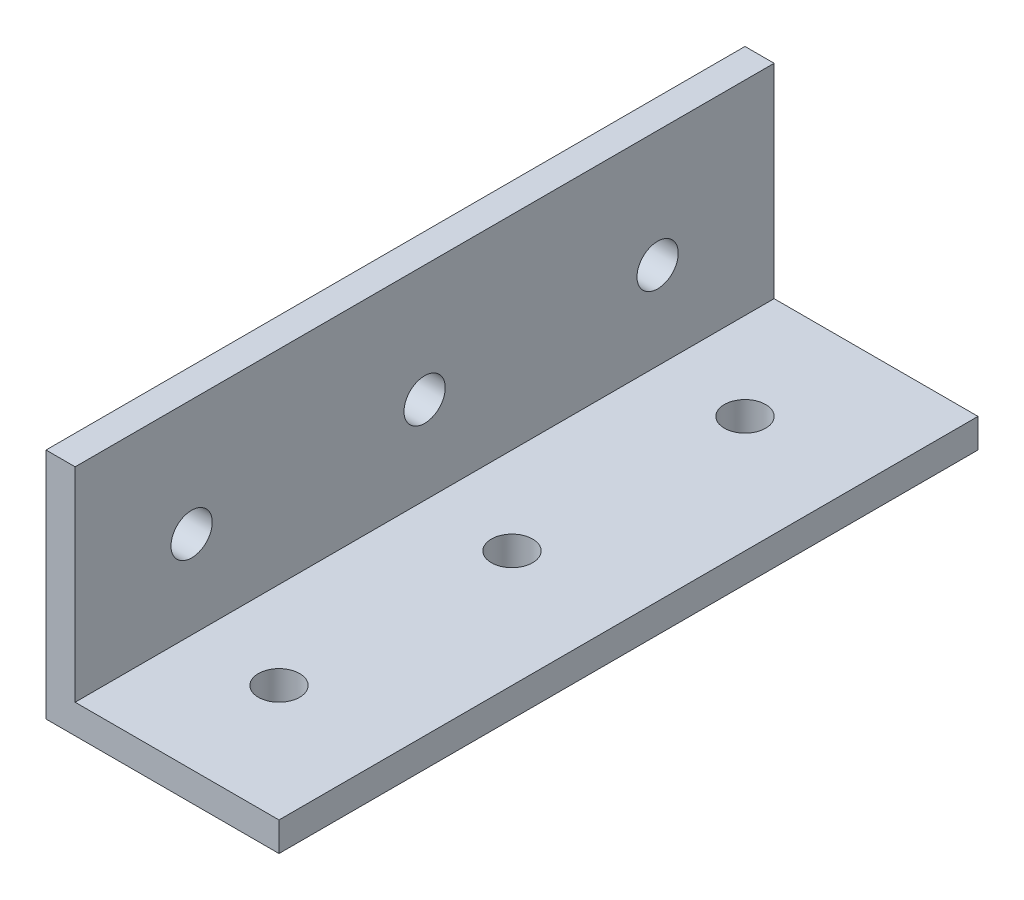
SolidWorks part; units mm, degrees
material "6061-T6 (SS)"
ref_plane "Front Plane" through (0, 0, 0) normal (0, 0, 1) x (1, 0, 0)
ref_plane "Top Plane" through (0, 0, 0) normal (0, 1, 0) x (1, 0, 0)
ref_plane "Right Plane" through (0, 0, 0) normal (1, 0, 0) x (0, 0, -1)
sketch "Sketch1" plane through (0, 0, 0) normal (0, 0, 1) x (1, 0, 0)
  line L1 (0, 0) -> (25.4, 0)
  line L2 (0, 0) -> (0, 25.4)
  line L3 (0, 25.4) -> (3.175, 25.4)
  line L4 (25.4, 0) -> (25.4, 3.175)
  line L7 (25.4, 3.175) -> (3.175, 3.175)
  line L8 (3.175, 25.4) -> (3.175, 3.175)
  dimension "D1" = 25.4
  dimension "D2" = 25.4
  dimension "D3" = 3.175
  dimension "D4" = 3.175
extrude "Boss-Extrude1" add sketch "Sketch1" along normal blind 76.2
hole_wizard "#8 Clearance Hole1" positions "Sketch3" profile "Sketch2" hole size "#8" standard "ANSI Inch" end condition through all
sketch "Sketch3" plane through (0, 0, 0) normal (0, -1, 0) x (1, 0, 0)
  line L0 (0, 76.2) -> (25.4, 76.2) construction
  line L1 (25.4, 76.2) -> (25.4, 0) construction
  point P0 (12.7, 63.5)
  point P2 (12.7, 38.1)
  point P4 (12.7, 12.7)
  dimension "D1" = 25.4
  dimension "D2" = 25.4
  dimension "D3" = 12.7
  dimension "D4" = 12.7
sketch "Sketch2" plane through (12.7, 0, 63.5) normal (1, 0, 0) x (0, 0, -1)
  line L0 (0, 0) -> (0, 25.4)
  line L1 (0, 25.4) -> (2.2479, 25.4)
  line L2 (2.2479, 25.4) -> (2.2479, 0)
  line L5 (2.2479, 0) -> (0, 0)
  line L11 (0, -6.35) -> (0, 107.95) construction
  dimension "Thru Hole Dia." = 4.4958
  dimension "Thru Hole Depth" = 25.4
hole_wizard "#8 Clearance Hole2" positions "Sketch5" profile "Sketch4" hole size "#8" standard "ANSI Inch" end condition through all
sketch "Sketch5" plane through (0, 0, 0) normal (-1, 0, 0) x (0, 0, 1)
  line L0 (0, 25.4) -> (0, 0) construction
  line L1 (76.2, 0) -> (0, 0) construction
  point P0 (63.5, 12.7)
  point P2 (38.1, 12.7)
  point P4 (12.7, 12.7)
  dimension "D1" = 25.4
  dimension "D2" = 25.4
  dimension "D3" = 12.7
  dimension "D4" = 12.7
sketch "Sketch4" plane through (0, 12.7, 63.5) normal (0, 1, 0) x (0, 0, 1)
  line L0 (0, 0) -> (0, 25.4)
  line L1 (0, 25.4) -> (2.2479, 25.4)
  line L2 (2.2479, 25.4) -> (2.2479, 0)
  line L5 (2.2479, 0) -> (0, 0)
  line L11 (0, -6.35) -> (0, 107.95) construction
  dimension "Thru Hole Dia." = 4.4958
  dimension "Thru Hole Depth" = 25.4
